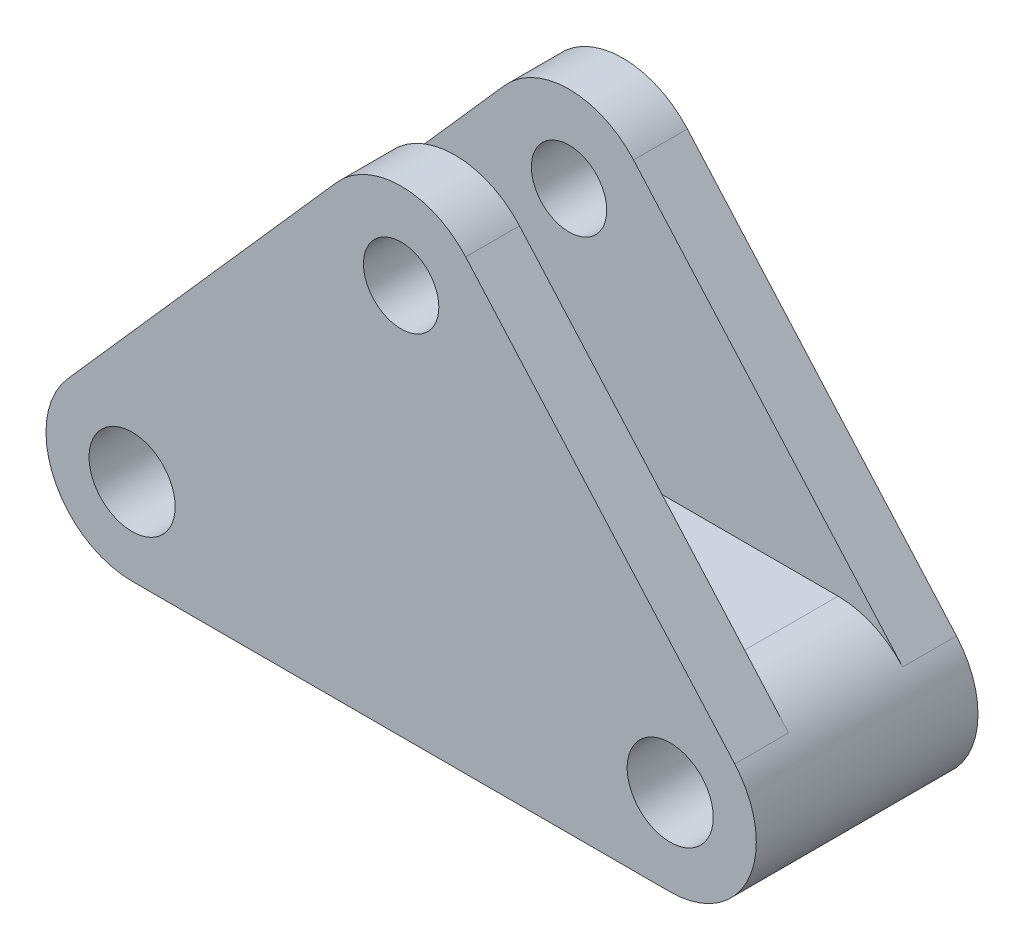
SolidWorks part; units mm, degrees
material "ABS"
ref_plane "Front Plane" through (0, 0, 0) normal (0, 0, 1) x (1, 0, 0)
ref_plane "Top Plane" through (0, 0, 0) normal (0, 1, 0) x (1, 0, 0)
ref_plane "Right Plane" through (0, 0, 0) normal (1, 0, 0) x (0, 0, -1)
sketch "Sketch1" plane through (0, 0, 0) normal (0, 0, 1) x (1, 0, 0)
  line L0 (0, 27.2364) -> (0, -32.7408) construction
  line L1 (25, -36.3) -> (-25, -36.3)
  line L2 (-30.9956, -23.0035) -> (-5.9956, 5.2965)
  line L3 (30.9956, -23.0035) -> (5.9956, 5.2965)
  line L4 (-25, -20.3) -> (25, -20.3)
  circle A0 centre (0, 0) radius 3.5
  circle A1 centre (0, 0) radius 11 construction
  circle A2 centre (-25, -28.3) radius 4
  arc A3 (-25, -36.3) -> (-30.9956, -23.0035) centre (-25, -28.3) cw
  arc A4 (-5.9956, 5.2965) -> (5.9956, 5.2965) centre (0, 0) cw
  arc A5 (25, -36.3) -> (30.9956, -23.0035) centre (25, -28.3) ccw
  circle A6 centre (25, -28.3) radius 4
  arc A7 (-25, -20.3) -> (-30.9956, -23.0035) centre (-25, -28.3) ccw
  arc A8 (25, -20.3) -> (30.9956, -23.0035) centre (25, -28.3) cw
  point P8 (0, 11)
  point P15 (0, -36.3)
  point P21 (0, -20.3)
  dimension "D1" = 7
  dimension "D2" = 22
  dimension "D3" = 8
  dimension "D6" = 8
  dimension "D7" = 8
  dimension "D4" = 25
  dimension "D5" = 39.3
extrude "Boss-Extrude1" add sketch "Sketch1" against normal blind 5 contours L0 L4 A7 A3 L1 A2 | L4 L0 L1 A5 A8 A6 | A1 L0 L4 A8 L3 | A4 L0 A0 A1 L3 | L0 A4 L2 A1 A0 | L0 A1 L2 A7 L4 region at (0, -28.3, 0) region at (0, -10.356, 0)
extrude "Boss-Extrude2" add sketch "Sketch1<3>" against normal blind 10.6 from vertex contours L0 L4 A7 A3 L1 A2 | L4 L0 L1 A5 A8 A6 region at (0, -28.3, 0) starting at point (-30.9956, -23.0035, -5)
sketch "Sketch1<3>" plane through (0, 0, 0) normal (0, 0, 1) x (1, 0, 0) same geometry as "Sketch1"
extrude "Boss-Extrude3" add sketch "Sketch1<4>" against normal blind 5 from vertex contours L0 A1 L2 A7 L4 | L0 A4 L2 A1 A0 | A4 L0 A0 A1 L3 | A1 L0 L4 A8 L3 | L4 L0 L1 A5 A8 A6 | L0 L4 A7 A3 L1 A2 region at (0, -28.3, 0) region at (0, -10.356, 0) starting at point (-25, -36.3, -15.6)
sketch "Sketch1<4>" plane through (0, 0, 0) normal (0, 0, 1) x (1, 0, 0) same geometry as "Sketch1"
equation "\"rod_diameter\"= 8"
equation "\"rod_hole_thickness\"= 4"
equation "\"rod_radius\"= \"rod_diameter\" / 2"
equation "\"platter_diameter\"= 320"
equation "\"platter_radius\"= \"platter_diameter\" / 2"
equation "\"extruder_mount_hole_spacing\"= 75"
equation "\"arm_rod_spacing\"= 40"
equation "\"top_frame_rod_spacing\"= \"arm_rod_spacing\" + 40"
equation "\"motor_level_rod_spacing\"= 15"
equation "\"linear_bearing_diameter\"= 15"
equation "\"z_rod_spacing\"= 75"
equation "\"platter_rod_spacing\"= 50"
equation "\"rod_nut_thickness\"= 6.5"
equation "\"rod_nut_inscribed_diameter\"= 13"
equation "\"z_height\"= 400"
equation "\"D1@Sketch1\"=\"rod_diameter\"-1"
equation "\"D3@Sketch1\"=\"rod_diameter\""
equation "\"D4@Sketch1\"=\"platter_rod_spacing\"/2"
equation "\"D6@Sketch1\"=\"rod_radius\"+\"rod_hole_thickness\""
equation "\"D7@Sketch1\"=\"rod_radius\"+\"rod_hole_thickness\""
